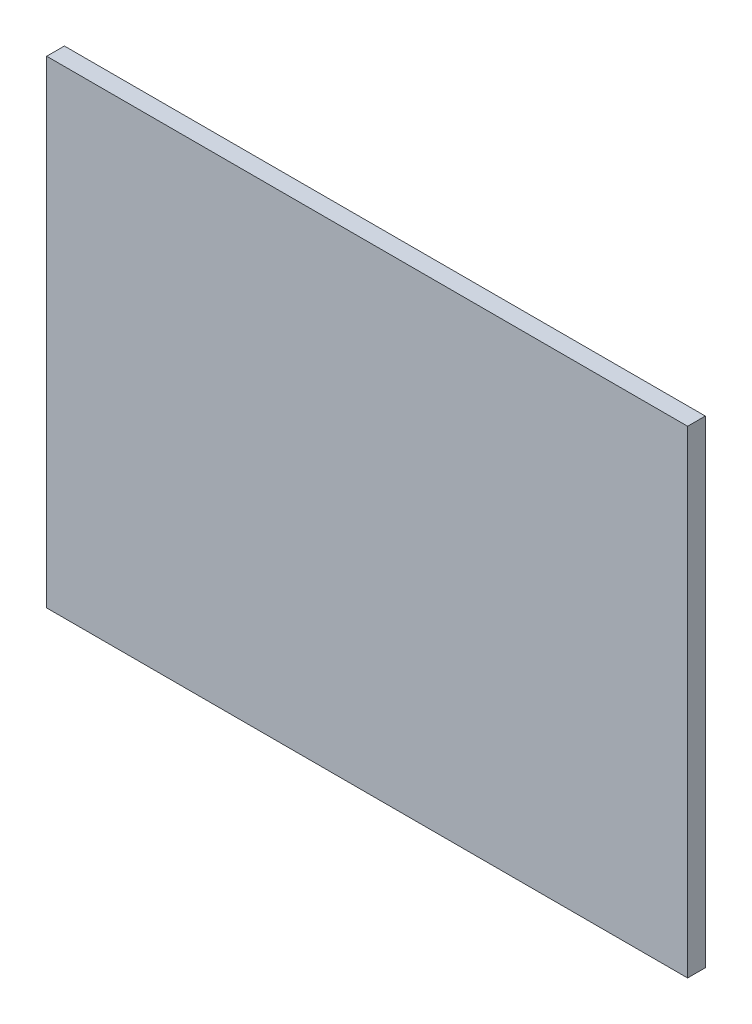
SolidWorks part; units mm, degrees
ref_plane "Front Plane" through (0, 0, 0) normal (0, 0, 1) x (1, 0, 0)
ref_plane "Top Plane" through (0, 0, 0) normal (0, 1, 0) x (1, 0, 0)
ref_plane "Right Plane" through (0, 0, 0) normal (1, 0, 0) x (0, 0, -1)
sketch "Sketch1" plane through (0, 0, 0) normal (0, 0, 1) x (1, 0, 0)
  line L1 (90.6195, 155.575) -> (-139.3499, 155.575)
  line L2 (90.6195, 155.575) -> (90.6195, -15.875)
  line L3 (90.6195, -15.875) -> (-139.3499, -15.875)
  line L4 (-139.3499, 155.575) -> (-139.3499, -15.875)
extrude "Boss-Extrude1" add sketch "Sketch1" along normal blind 6.35
